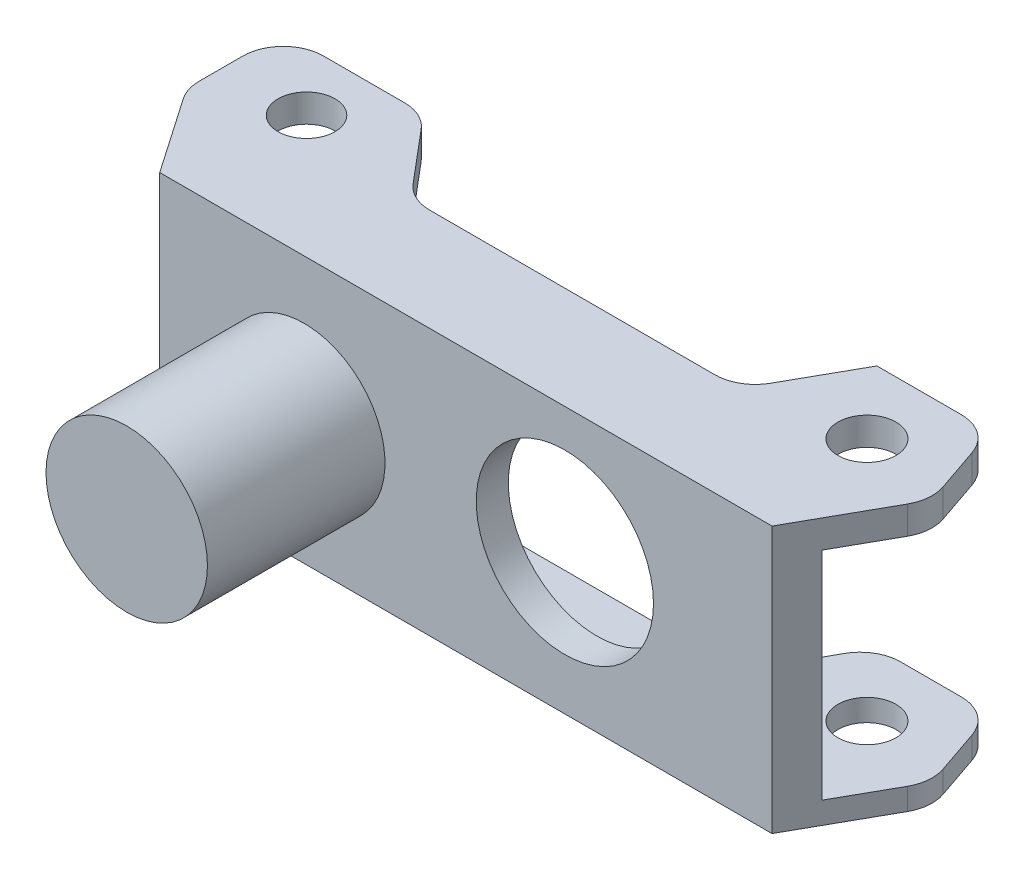
SolidWorks part; units mm, degrees
material "Cast Carbon Steel"
ref_plane "Front Plane" through (0, 0, 0) normal (0, 0, 1) x (1, 0, 0)
ref_plane "Top Plane" through (0, 0, 0) normal (0, 1, 0) x (1, 0, 0)
ref_plane "Right Plane" through (0, 0, 0) normal (1, 0, 0) x (0, 0, -1)
other "Configuration Table"
sketch "Sketch1" plane through (0, 0, 0) normal (0, 0, 1) x (1, 0, 0)
  circle A0 centre (2, -17.2271) radius 10
extrude "Extrude1" add sketch "Sketch1" along normal blind 15
sketch "Sketch2" plane through (0, 0, 0) normal (0, 0, -1) x (-1, 0, 0)
  circle A0 centre (-2, -17.2271) radius 10
extrude "Extrude2" add sketch "Sketch2" along normal blind 7
sketch "Sketch5" plane through (0, 0, 0) normal (0, 1, 0) x (1, 0, 0)
  line L0 (-15.9079, 7) -> (-23.2644, 17.6762)
  line L1 (12, 7) -> (-8, 7) construction
  line L2 (-23.2644, 17.6762) -> (-23.2644, 29.6517)
  line L3 (-23.2644, 29.6517) -> (-5.8846, 29.6517)
  line L4 (-5.8846, 29.6517) -> (2.5101, 19.6909)
  line L5 (2.5101, 19.6909) -> (43.1144, 19.6909)
  line L6 (43.1144, 19.6909) -> (49.2733, 30.6782)
  line L7 (49.2733, 30.6782) -> (63.3018, 30.6782)
  line L8 (63.3018, 30.6782) -> (67.0656, 19.6909)
  line L9 (67.0656, 19.6909) -> (59.9517, 7)
  line L10 (59.9517, 7) -> (-15.9079, 7)
extrude "Extrude5" add sketch "Sketch5" against normal blind 33
sketch "Sketch6" plane through (-23.2644, 0, 0) normal (-1, 0, 0) x (0, 0, 1)
  line L1 (-32.8437, -30.2847) -> (-10.9726, -30.2847)
  line L2 (-32.8437, -30.2847) -> (-32.8437, -3.4599)
  line L3 (-32.8437, -3.4599) -> (-10.9726, -3.4599)
  line L4 (-10.9726, -30.2847) -> (-10.9726, -3.4599)
extrude "Cut-Extrude1" cut sketch "Sketch6" against normal through all
sketch "Sketch7" plane through (0, 0, 0) normal (0, 1, 0) x (-1, 0, 0)
  circle A0 centre (12.9639, -22.2438) radius 3.531
  circle A1 centre (-56.4705, -22.2438) radius 3.5941
extrude "Cut-Extrude2" cut sketch "Sketch7" against normal through all
ref_axis "Axis1" through (2, -17.2271, 15) along (0, 0, -1)
fillet "Fillet6" radius 5 15 edges at (67.0656, -31.6423, -19.6909) (67.0656, -1.73, -19.6909) (63.3018, -1.73, -30.6782) (63.3018, -31.6423, -30.6782) (49.2733, -31.6423, -30.6782) (43.1144, -31.6423, -19.6909) (43.1144, -1.73, -19.6909) (2.5101, -31.6423, -19.6909) (2.5101, -1.73, -19.6909) (-5.8846, -1.73, -29.6517) (-5.8846, -31.6423, -29.6517) (-23.2644, -31.6423, -17.6762) (-23.2644, -1.73, -17.6762) (-23.2644, -1.73, -29.6517) (-23.2644, -31.6423, -29.6517)
sketch "Sketch8" plane through (0, 0, -7) normal (0, 0, 1) x (1, 0, 0)
  circle A0 centre (34.2854, -15.6525) radius 10.981
extrude "Cut-Extrude3" cut sketch "Sketch8" against normal through all
ref_plane "Plane1" through (0, -16.8747, 0) normal (0, 1, 0) x (-1, 0, 0)
